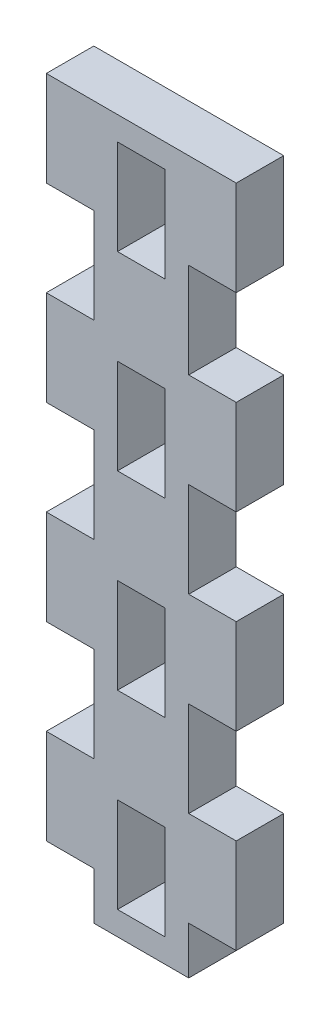
SolidWorks part; units mm, degrees
material "ﾁｰｸ材"
ref_plane "正面" through (0, 0, 0) normal (0, 0, 1) x (1, 0, 0)
ref_plane "平面" through (0, 0, 0) normal (0, 1, 0) x (1, 0, 0)
ref_plane "右側面" through (0, 0, 0) normal (1, 0, 0) x (0, 0, -1)
sketch "ｽｹｯﾁ1" plane through (0, 0, 0) normal (0, 0, 1) x (1, 0, 0)
  line L1 (10, 37.5) -> (-10, 37.5)
  line L2 (10, 37.5) -> (10, -37.5)
  line L3 (10, -37.5) -> (-10, -37.5)
  line L4 (-10, 37.5) -> (-10, -37.5)
  line L5 (10, 37.5) -> (-10, -37.5) construction
  line L6 (10, -37.5) -> (-10, 37.5) construction
  point P0 (0, 0)
  dimension "D1" = 20
  dimension "D2" = 75
extrude "ﾎﾞｽ - 押し出し1" add sketch "ｽｹｯﾁ1" along normal blind 5
sketch "ｽｹｯﾁ2" plane through (0, 0, 5) normal (0, 0, 1) x (1, 0, 0)
  line L0 (-10, 37.5) -> (-10, -37.5) construction
  line L1 (-10, 27.5) -> (-5, 27.5)
  line L2 (-10, 27.5) -> (-10, 17.5)
  line L3 (-10, 17.5) -> (-5, 17.5)
  line L4 (-5, 27.5) -> (-5, 17.5)
  line L5 (10, 37.5) -> (-10, 37.5) construction
  line L6 (-10, 7.5) -> (-10, -2.5)
  line L7 (-10, 7.5) -> (-5, 7.5)
  line L8 (-5, 7.5) -> (-5, -2.5)
  line L9 (-10, -2.5) -> (-5, -2.5)
  line L10 (-10, -12.5) -> (-10, -22.5)
  line L11 (-10, -12.5) -> (-5, -12.5)
  line L12 (-5, -12.5) -> (-5, -22.5)
  line L13 (-10, -22.5) -> (-5, -22.5)
  line L14 (-10, -32.5) -> (-10, -42.5)
  line L15 (-10, -32.5) -> (-5, -32.5)
  line L16 (-5, -32.5) -> (-5, -42.5)
  line L17 (-10, -42.5) -> (-5, -42.5)
  line L18 (0, 0) -> (0, 9.1802) construction
  line L19 (10, -32.5) -> (5, -32.5)
  line L20 (5, -32.5) -> (5, -42.5)
  line L21 (10, -42.5) -> (5, -42.5)
  line L22 (10, -32.5) -> (10, -42.5)
  line L23 (10, -12.5) -> (5, -12.5)
  line L24 (5, -12.5) -> (5, -22.5)
  line L25 (10, -22.5) -> (5, -22.5)
  line L26 (10, -12.5) -> (10, -22.5)
  line L27 (10, 7.5) -> (5, 7.5)
  line L28 (5, 7.5) -> (5, -2.5)
  line L29 (10, -2.5) -> (5, -2.5)
  line L30 (10, 7.5) -> (10, -2.5)
  line L31 (10, 17.5) -> (5, 17.5)
  line L32 (5, 27.5) -> (5, 17.5)
  line L33 (10, 27.5) -> (5, 27.5)
  line L34 (10, 27.5) -> (10, 17.5)
  dimension "D1" = 10
  dimension "D2" = 5
  dimension "D3" = 10
  dimension "D4" = 4
extrude "ｶｯﾄ - 押し出し1" cut sketch "ｽｹｯﾁ2" against normal through all
sketch "ｽｹｯﾁ3" plane through (0, 0, 5) normal (0, 0, 1) x (1, 0, 0)
  line L0 (-5, -37.5) -> (5, -37.5) construction
  line L1 (-2.5, -35) -> (2.5, -35)
  line L2 (-2.5, -35) -> (-2.5, -25)
  line L3 (-2.5, -25) -> (2.5, -25)
  line L4 (2.5, -35) -> (2.5, -25)
  line L5 (-2.5, -35) -> (2.5, -25) construction
  line L6 (-2.5, -25) -> (2.5, -35) construction
  line L7 (-2.5, -15) -> (-2.5, -5)
  line L8 (-2.5, -15) -> (2.5, -15)
  line L9 (2.5, -15) -> (2.5, -5)
  line L10 (-2.5, -5) -> (2.5, -5)
  line L11 (-2.5, 5) -> (-2.5, 15)
  line L12 (-2.5, 5) -> (2.5, 5)
  line L13 (2.5, 5) -> (2.5, 15)
  line L14 (-2.5, 15) -> (2.5, 15)
  line L15 (-2.5, 25) -> (-2.5, 35)
  line L16 (-2.5, 25) -> (2.5, 25)
  line L17 (2.5, 25) -> (2.5, 35)
  line L18 (-2.5, 35) -> (2.5, 35)
  point P0 (0, -30)
  dimension "D1" = 2.5
  dimension "D2" = 5
  dimension "D3" = 10
  dimension "D4" = 4
extrude "ｶｯﾄ - 押し出し2" cut sketch "ｽｹｯﾁ3" against normal through all
